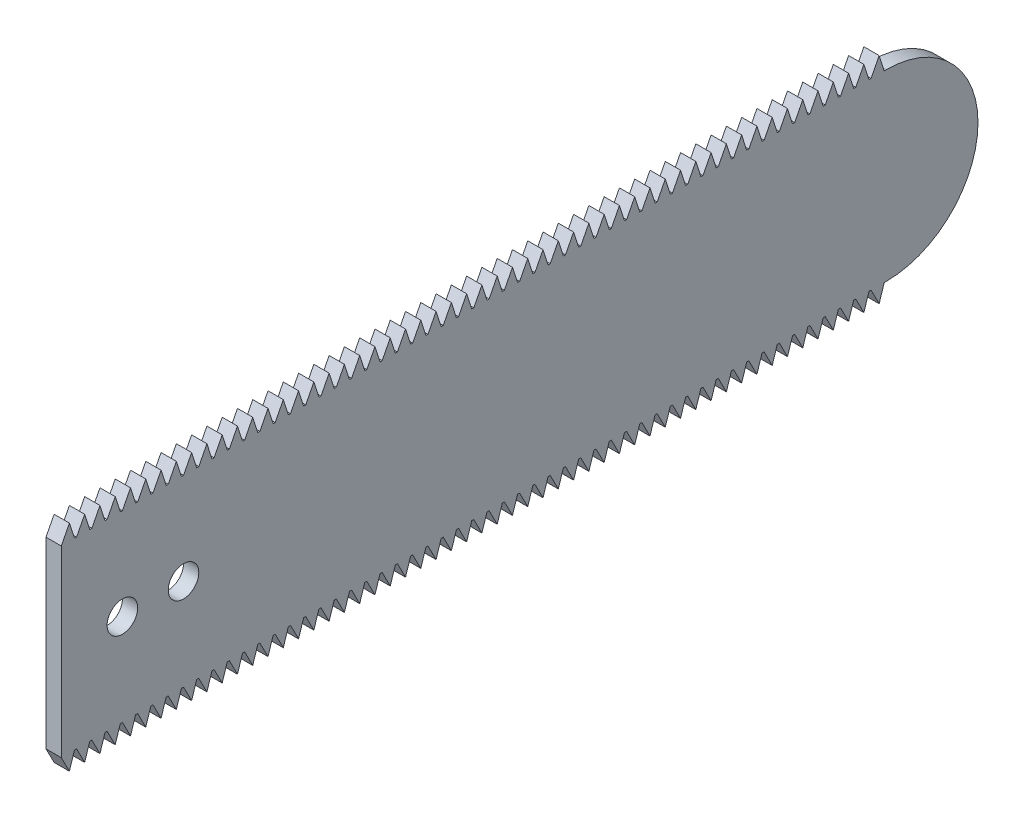
SolidWorks part; units mm, degrees
ref_plane "Ebene vorne" through (0, 0, 0) normal (0, 0, 1) x (1, 0, 0)
ref_plane "Ebene oben" through (0, 0, 0) normal (0, 1, 0) x (1, 0, 0)
ref_plane "Ebene rechts" through (0, 0, 0) normal (1, 0, 0) x (0, 0, -1)
sketch "Skizze1" plane through (0, 0, 0) normal (1, 0, 0) x (0, 0, -1)
  line L5 (-5252.319, 1638.1551) -> (-4952.319, 1638.1551)
  line L6 (-5252.319, 1638.1551) -> (-5252.319, 1578.1551)
  line L7 (-5252.319, 1578.1551) -> (-4952.319, 1578.1551)
  line L8 (-4952.319, 1638.1551) -> (-4952.319, 1578.1551)
  dimension "D1" = 300
  dimension "D2" = 60
extrude "Aufsatz-Linear austragen1" add sketch "Skizze1" along normal blind 5
sketch "Skizze2" plane through (5, 0, 0) normal (1, 0, 0) x (0, 0, -1)
  line L0 (-5252.319, 1638.1551) -> (-5252.319, 1578.1551) construction
  circle A0 centre (-5232.319, 1608.1551) radius 5
  circle A1 centre (-5212.319, 1608.1551) radius 5
  dimension "D1" = 20
  dimension "D2" = 20
extrude "Schnitt-Linear austragen1" cut sketch "Skizze2" against normal blind 5
fillet "Verrundung1" radius 30 2 edges at (2.5, 1578.1551, 4952.319) (2.5, 1638.1551, 4952.319)
sketch "Skizze3" plane through (5, 0, 0) normal (1, 0, 0) x (0, 0, -1)
  line L0 (-5252.319, 1638.1551) -> (-5249.6643, 1643.3277)
  line L1 (-5249.6643, 1643.3277) -> (-5248.0004, 1638.1551)
  line L2 (-4982.319, 1638.1551) -> (-5252.319, 1638.1551) construction
  line L3 (-5248.0004, 1638.1551) -> (-5252.319, 1638.1551)
  line L4 (-5243.0004, 1638.1551) -> (-5247.319, 1638.1551)
  line L5 (-5247.319, 1638.1551) -> (-5244.6643, 1643.3277)
  line L6 (-5244.6643, 1643.3277) -> (-5243.0004, 1638.1551)
  line L7 (-5238.0004, 1638.1551) -> (-5242.319, 1638.1551)
  line L8 (-5242.319, 1638.1551) -> (-5239.6643, 1643.3277)
  line L9 (-5239.6643, 1643.3277) -> (-5238.0004, 1638.1551)
  line L10 (-5233.0004, 1638.1551) -> (-5237.319, 1638.1551)
  line L11 (-5237.319, 1638.1551) -> (-5234.6643, 1643.3277)
  line L12 (-5234.6643, 1643.3277) -> (-5233.0004, 1638.1551)
  line L13 (-5228.0004, 1638.1551) -> (-5232.319, 1638.1551)
  line L14 (-5232.319, 1638.1551) -> (-5229.6643, 1643.3277)
  line L15 (-5229.6643, 1643.3277) -> (-5228.0004, 1638.1551)
  line L16 (-5223.0004, 1638.1551) -> (-5227.319, 1638.1551)
  line L17 (-5227.319, 1638.1551) -> (-5224.6643, 1643.3277)
  line L18 (-5224.6643, 1643.3277) -> (-5223.0004, 1638.1551)
  line L19 (-5218.0004, 1638.1551) -> (-5222.319, 1638.1551)
  line L20 (-5222.319, 1638.1551) -> (-5219.6643, 1643.3277)
  line L21 (-5219.6643, 1643.3277) -> (-5218.0004, 1638.1551)
  line L22 (-5213.0004, 1638.1551) -> (-5217.319, 1638.1551)
  line L23 (-5217.319, 1638.1551) -> (-5214.6643, 1643.3277)
  line L24 (-5214.6643, 1643.3277) -> (-5213.0004, 1638.1551)
  line L25 (-5208.0004, 1638.1551) -> (-5212.319, 1638.1551)
  line L26 (-5212.319, 1638.1551) -> (-5209.6643, 1643.3277)
  line L27 (-5209.6643, 1643.3277) -> (-5208.0004, 1638.1551)
  line L28 (-5203.0004, 1638.1551) -> (-5207.319, 1638.1551)
  line L29 (-5207.319, 1638.1551) -> (-5204.6643, 1643.3277)
  line L30 (-5204.6643, 1643.3277) -> (-5203.0004, 1638.1551)
  line L31 (-5198.0004, 1638.1551) -> (-5202.319, 1638.1551)
  line L32 (-5202.319, 1638.1551) -> (-5199.6643, 1643.3277)
  line L33 (-5199.6643, 1643.3277) -> (-5198.0004, 1638.1551)
  line L34 (-5193.0004, 1638.1551) -> (-5197.319, 1638.1551)
  line L35 (-5197.319, 1638.1551) -> (-5194.6643, 1643.3277)
  line L36 (-5194.6643, 1643.3277) -> (-5193.0004, 1638.1551)
  line L37 (-5188.0004, 1638.1551) -> (-5192.319, 1638.1551)
  line L38 (-5192.319, 1638.1551) -> (-5189.6643, 1643.3277)
  line L39 (-5189.6643, 1643.3277) -> (-5188.0004, 1638.1551)
  line L40 (-5183.0004, 1638.1551) -> (-5187.319, 1638.1551)
  line L41 (-5187.319, 1638.1551) -> (-5184.6643, 1643.3277)
  line L42 (-5184.6643, 1643.3277) -> (-5183.0004, 1638.1551)
  line L43 (-5178.0004, 1638.1551) -> (-5182.319, 1638.1551)
  line L44 (-5182.319, 1638.1551) -> (-5179.6643, 1643.3277)
  line L45 (-5179.6643, 1643.3277) -> (-5178.0004, 1638.1551)
  line L46 (-5173.0004, 1638.1551) -> (-5177.319, 1638.1551)
  line L47 (-5177.319, 1638.1551) -> (-5174.6643, 1643.3277)
  line L48 (-5174.6643, 1643.3277) -> (-5173.0004, 1638.1551)
  line L49 (-5168.0004, 1638.1551) -> (-5172.319, 1638.1551)
  line L50 (-5172.319, 1638.1551) -> (-5169.6643, 1643.3277)
  line L51 (-5169.6643, 1643.3277) -> (-5168.0004, 1638.1551)
  line L52 (-5163.0004, 1638.1551) -> (-5167.319, 1638.1551)
  line L53 (-5167.319, 1638.1551) -> (-5164.6643, 1643.3277)
  line L54 (-5164.6643, 1643.3277) -> (-5163.0004, 1638.1551)
  line L55 (-5158.0004, 1638.1551) -> (-5162.319, 1638.1551)
  line L56 (-5162.319, 1638.1551) -> (-5159.6643, 1643.3277)
  line L57 (-5159.6643, 1643.3277) -> (-5158.0004, 1638.1551)
  line L58 (-5153.0004, 1638.1551) -> (-5157.319, 1638.1551)
  line L59 (-5157.319, 1638.1551) -> (-5154.6643, 1643.3277)
  line L60 (-5154.6643, 1643.3277) -> (-5153.0004, 1638.1551)
  line L61 (-5148.0004, 1638.1551) -> (-5152.319, 1638.1551)
  line L62 (-5152.319, 1638.1551) -> (-5149.6643, 1643.3277)
  line L63 (-5149.6643, 1643.3277) -> (-5148.0004, 1638.1551)
  line L64 (-5143.0004, 1638.1551) -> (-5147.319, 1638.1551)
  line L65 (-5147.319, 1638.1551) -> (-5144.6643, 1643.3277)
  line L66 (-5144.6643, 1643.3277) -> (-5143.0004, 1638.1551)
  line L67 (-5138.0004, 1638.1551) -> (-5142.319, 1638.1551)
  line L68 (-5142.319, 1638.1551) -> (-5139.6643, 1643.3277)
  line L69 (-5139.6643, 1643.3277) -> (-5138.0004, 1638.1551)
  line L70 (-5133.0004, 1638.1551) -> (-5137.319, 1638.1551)
  line L71 (-5137.319, 1638.1551) -> (-5134.6643, 1643.3277)
  line L72 (-5134.6643, 1643.3277) -> (-5133.0004, 1638.1551)
  line L73 (-5128.0004, 1638.1551) -> (-5132.319, 1638.1551)
  line L74 (-5132.319, 1638.1551) -> (-5129.6643, 1643.3277)
  line L75 (-5129.6643, 1643.3277) -> (-5128.0004, 1638.1551)
  line L76 (-5123.0004, 1638.1551) -> (-5127.319, 1638.1551)
  line L77 (-5127.319, 1638.1551) -> (-5124.6643, 1643.3277)
  line L78 (-5124.6643, 1643.3277) -> (-5123.0004, 1638.1551)
  line L79 (-5118.0004, 1638.1551) -> (-5122.319, 1638.1551)
  line L80 (-5122.319, 1638.1551) -> (-5119.6643, 1643.3277)
  line L81 (-5119.6643, 1643.3277) -> (-5118.0004, 1638.1551)
  line L82 (-5113.0004, 1638.1551) -> (-5117.319, 1638.1551)
  line L83 (-5117.319, 1638.1551) -> (-5114.6643, 1643.3277)
  line L84 (-5114.6643, 1643.3277) -> (-5113.0004, 1638.1551)
  line L85 (-5108.0004, 1638.1551) -> (-5112.319, 1638.1551)
  line L86 (-5112.319, 1638.1551) -> (-5109.6643, 1643.3277)
  line L87 (-5109.6643, 1643.3277) -> (-5108.0004, 1638.1551)
  line L88 (-5103.0004, 1638.1551) -> (-5107.319, 1638.1551)
  line L89 (-5107.319, 1638.1551) -> (-5104.6643, 1643.3277)
  line L90 (-5104.6643, 1643.3277) -> (-5103.0004, 1638.1551)
  line L91 (-5098.0004, 1638.1551) -> (-5102.319, 1638.1551)
  line L92 (-5102.319, 1638.1551) -> (-5099.6643, 1643.3277)
  line L93 (-5099.6643, 1643.3277) -> (-5098.0004, 1638.1551)
  line L94 (-5093.0004, 1638.1551) -> (-5097.319, 1638.1551)
  line L95 (-5097.319, 1638.1551) -> (-5094.6643, 1643.3277)
  line L96 (-5094.6643, 1643.3277) -> (-5093.0004, 1638.1551)
  line L97 (-5088.0004, 1638.1551) -> (-5092.319, 1638.1551)
  line L98 (-5092.319, 1638.1551) -> (-5089.6643, 1643.3277)
  line L99 (-5089.6643, 1643.3277) -> (-5088.0004, 1638.1551)
  line L100 (-5083.0004, 1638.1551) -> (-5087.319, 1638.1551)
  line L101 (-5087.319, 1638.1551) -> (-5084.6643, 1643.3277)
  line L102 (-5084.6643, 1643.3277) -> (-5083.0004, 1638.1551)
  line L103 (-5078.0004, 1638.1551) -> (-5082.319, 1638.1551)
  line L104 (-5082.319, 1638.1551) -> (-5079.6643, 1643.3277)
  line L105 (-5079.6643, 1643.3277) -> (-5078.0004, 1638.1551)
  line L106 (-5073.0004, 1638.1551) -> (-5077.319, 1638.1551)
  line L107 (-5077.319, 1638.1551) -> (-5074.6643, 1643.3277)
  line L108 (-5074.6643, 1643.3277) -> (-5073.0004, 1638.1551)
  line L109 (-5068.0004, 1638.1551) -> (-5072.319, 1638.1551)
  line L110 (-5072.319, 1638.1551) -> (-5069.6643, 1643.3277)
  line L111 (-5069.6643, 1643.3277) -> (-5068.0004, 1638.1551)
  line L112 (-5063.0004, 1638.1551) -> (-5067.319, 1638.1551)
  line L113 (-5067.319, 1638.1551) -> (-5064.6643, 1643.3277)
  line L114 (-5064.6643, 1643.3277) -> (-5063.0004, 1638.1551)
  line L115 (-5058.0004, 1638.1551) -> (-5062.319, 1638.1551)
  line L116 (-5062.319, 1638.1551) -> (-5059.6643, 1643.3277)
  line L117 (-5059.6643, 1643.3277) -> (-5058.0004, 1638.1551)
  line L118 (-5053.0004, 1638.1551) -> (-5057.319, 1638.1551)
  line L119 (-5057.319, 1638.1551) -> (-5054.6643, 1643.3277)
  line L120 (-5054.6643, 1643.3277) -> (-5053.0004, 1638.1551)
  line L121 (-5048.0004, 1638.1551) -> (-5052.319, 1638.1551)
  line L122 (-5052.319, 1638.1551) -> (-5049.6643, 1643.3277)
  line L123 (-5049.6643, 1643.3277) -> (-5048.0004, 1638.1551)
  line L124 (-5043.0004, 1638.1551) -> (-5047.319, 1638.1551)
  line L125 (-5047.319, 1638.1551) -> (-5044.6643, 1643.3277)
  line L126 (-5044.6643, 1643.3277) -> (-5043.0004, 1638.1551)
  line L127 (-5038.0004, 1638.1551) -> (-5042.319, 1638.1551)
  line L128 (-5042.319, 1638.1551) -> (-5039.6643, 1643.3277)
  line L129 (-5039.6643, 1643.3277) -> (-5038.0004, 1638.1551)
  line L130 (-5033.0004, 1638.1551) -> (-5037.319, 1638.1551)
  line L131 (-5037.319, 1638.1551) -> (-5034.6643, 1643.3277)
  line L132 (-5034.6643, 1643.3277) -> (-5033.0004, 1638.1551)
  line L133 (-5028.0004, 1638.1551) -> (-5032.319, 1638.1551)
  line L134 (-5032.319, 1638.1551) -> (-5029.6643, 1643.3277)
  line L135 (-5029.6643, 1643.3277) -> (-5028.0004, 1638.1551)
  line L136 (-5023.0004, 1638.1551) -> (-5027.319, 1638.1551)
  line L137 (-5027.319, 1638.1551) -> (-5024.6643, 1643.3277)
  line L138 (-5024.6643, 1643.3277) -> (-5023.0004, 1638.1551)
  line L139 (-5018.0004, 1638.1551) -> (-5022.319, 1638.1551)
  line L140 (-5022.319, 1638.1551) -> (-5019.6643, 1643.3277)
  line L141 (-5019.6643, 1643.3277) -> (-5018.0004, 1638.1551)
  line L142 (-5013.0004, 1638.1551) -> (-5017.319, 1638.1551)
  line L143 (-5017.319, 1638.1551) -> (-5014.6643, 1643.3277)
  line L144 (-5014.6643, 1643.3277) -> (-5013.0004, 1638.1551)
  line L145 (-5008.0004, 1638.1551) -> (-5012.319, 1638.1551)
  line L146 (-5012.319, 1638.1551) -> (-5009.6643, 1643.3277)
  line L147 (-5009.6643, 1643.3277) -> (-5008.0004, 1638.1551)
  line L148 (-5003.0004, 1638.1551) -> (-5007.319, 1638.1551)
  line L149 (-5007.319, 1638.1551) -> (-5004.6643, 1643.3277)
  line L150 (-5004.6643, 1643.3277) -> (-5003.0004, 1638.1551)
  line L151 (-4998.0004, 1638.1551) -> (-5002.319, 1638.1551)
  line L152 (-5002.319, 1638.1551) -> (-4999.6643, 1643.3277)
  line L153 (-4999.6643, 1643.3277) -> (-4998.0004, 1638.1551)
  line L154 (-4993.0004, 1638.1551) -> (-4997.319, 1638.1551)
  line L155 (-4997.319, 1638.1551) -> (-4994.6643, 1643.3277)
  line L156 (-4994.6643, 1643.3277) -> (-4993.0004, 1638.1551)
  line L157 (-4988.0004, 1638.1551) -> (-4992.319, 1638.1551)
  line L158 (-4992.319, 1638.1551) -> (-4989.6643, 1643.3277)
  line L159 (-4989.6643, 1643.3277) -> (-4988.0004, 1638.1551)
  line L160 (-4983.0004, 1638.1551) -> (-4987.319, 1638.1551)
  line L161 (-4987.319, 1638.1551) -> (-4984.6643, 1643.3277)
  line L162 (-4984.6643, 1643.3277) -> (-4983.0004, 1638.1551)
  dimension "D1" = 54
extrude "Aufsatz-Linear austragen2" add sketch "Skizze3" against normal blind 5
ref_plane "Ebene1" through (0, 1608.1551, 0) normal (0, -1, 0) x (-1, 0, 0)
mirror "Spiegeln1" about plane through (0, 1608.1551, 0) normal (0, -1, 0) of "Aufsatz-Linear austragen2"
